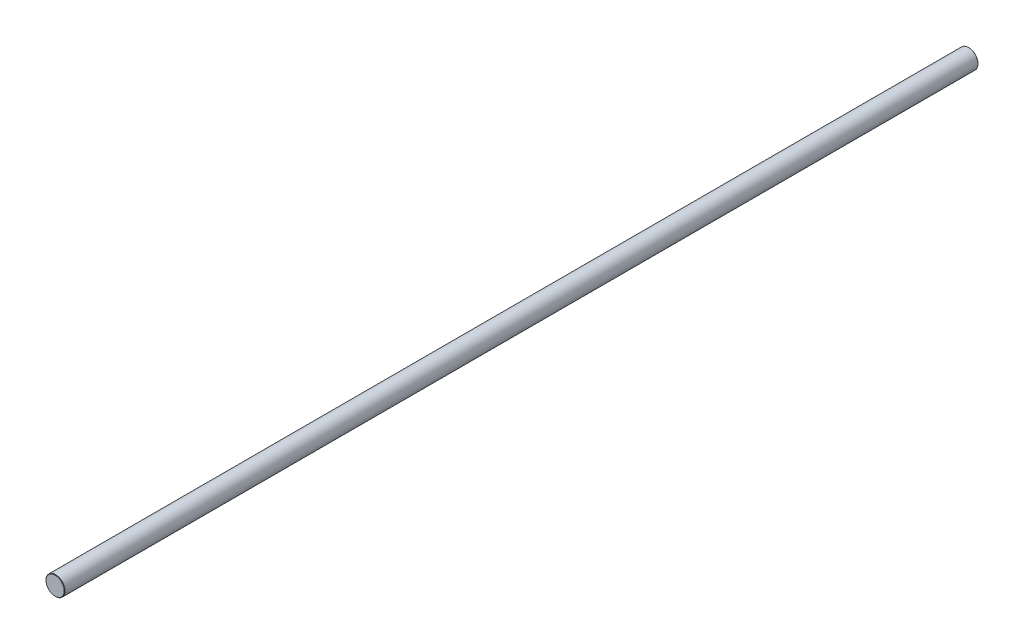
SolidWorks part; units mm, degrees
material "AISI 1055 Steel"
ref_plane "Front Plane" through (0, 0, 0) normal (0, 0, 1) x (1, 0, 0)
ref_plane "Top Plane" through (0, 0, 0) normal (0, 1, 0) x (1, 0, 0)
ref_plane "Right Plane" through (0, 0, 0) normal (1, 0, 0) x (0, 0, -1)
sketch "Sketch1" plane through (0, 0, 0) normal (0, 0, 1) x (1, 0, 0)
  circle A0 centre (0, 0) radius 12.5 construction
  dimension "Diameter" = 25
sketch "Sketch2" plane through (0, 0, 0) normal (1, 0, 0) x (0, 0, -1)
  line L0 (600, 0) -> (-600, 0) construction
  point P0 (-480, 0)
  point P3 (0, 0)
  point P4 (480, 0)
  point P6 (-420, 0)
  point P7 (420, 0)
  dimension "Length" = 1200
  dimension "D1" = 120
  dimension "D2" = 120
  dimension "D3" = 180
  dimension "D4" = 180
sketch "Sketch3" plane through (0, 0, 0) normal (0, 0, 1) x (1, 0, 0)
  circle A0 centre (0, 0) radius 12.5 construction
  circle A1 centre (0, 0) radius 12.5
extrude "Boss-Extrude1" add sketch "Sketch3" along normal up to vertex (600 mm away) and the other way up to vertex (600 mm away) up to point (0, 0, 600) other way up to point (0, 0, -600)
chamfer "Chamfer1" distance 0.5 angle 45 2 edges at (12.5, 0, 600) (12.5, 0, -600)
ref_axis "Axis" through (0, 0, -660) along (0, 0, 1)
equation "\"D1@Chamfer1\"=\"Diameter@Sketch1\"*.02"
equation "\"D1@Sketch2\"=\"D2@Sketch2\""
equation "\"D2@Sketch2\"=\"Length@Sketch2\"*.1"
equation "\"D3@Sketch2\"=\"Length@Sketch2\"*.15"
equation "\"D4@Sketch2\"=\"D3@Sketch2\""
